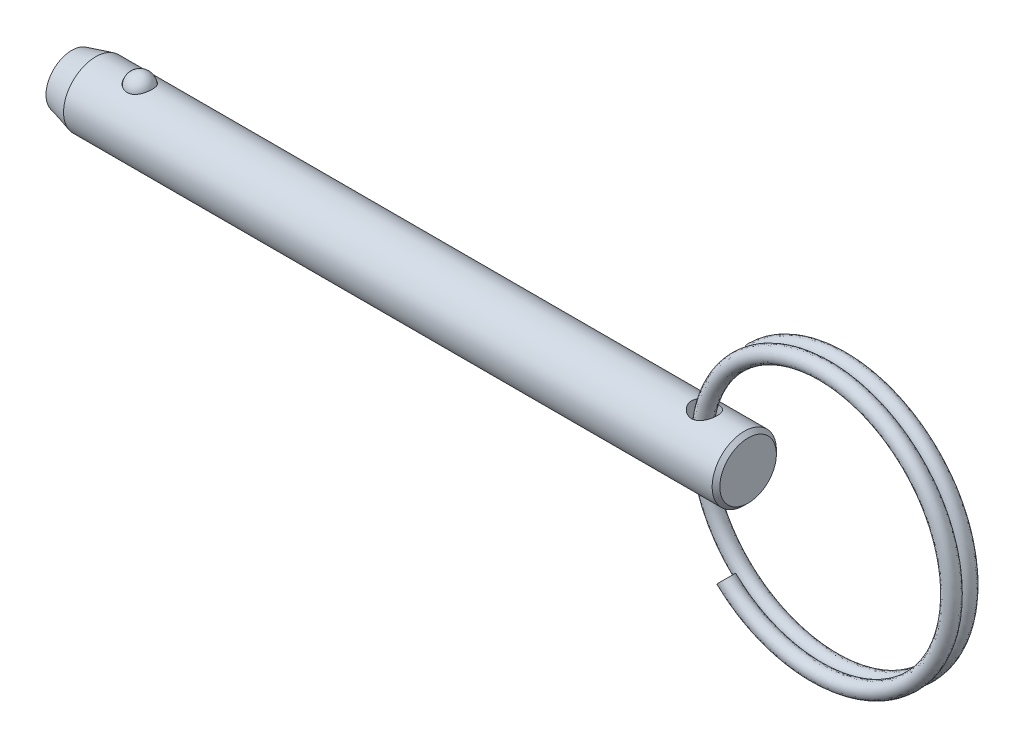
SolidWorks part; units mm, degrees
material "Plain Carbon Steel"
ref_plane "Front" through (0, 0, 0) normal (0, 0, 1) x (1, 0, 0)
ref_plane "Top" through (0, 0, 0) normal (0, 1, 0) x (1, 0, 0)
ref_plane "Right" through (0, 0, 0) normal (1, 0, 0) x (0, 0, -1)
sketch "Sketch1" plane through (0, 0, 0) normal (0, 0, 1) x (1, 0, 0)
  line L0 (33.4264, 2.794) -> (33.0454, 3.175)
  line L1 (33.0454, 3.175) -> (33.4264, 3.175) construction
  line L4 (33.4264, 2.794) -> (33.4264, 0)
  line L5 (33.4264, 3.175) -> (33.4264, 2.794) construction
  line L16 (33.0454, 3.175) -> (-31.0565, 3.175)
  line L17 (-33.4264, 3.175) -> (-33.4264, 2.54) construction
  line L19 (-31.0565, 3.175) -> (-33.4264, 3.175) construction
  line L22 (-33.4264, -3.175) -> (-31.0565, -3.175) construction
  line L23 (-26.6919, 2.8575) -> (-26.6919, -2.8575) construction
  line L24 (-33.4264, 0) -> (33.4264, 0)
  line L27 (33.4264, 0) -> (36.2204, 0) construction
  line L29 (-33.4264, 0) -> (-33.4264, -2.54) construction
  line L36 (27.8384, 0) -> (27.8384, 3.175) construction
  line L37 (-33.4264, 2.54) -> (-33.4264, 0)
  line L38 (-31.0565, -3.175) -> (33.4264, -3.175) construction
  line L39 (-33.4264, -2.54) -> (-33.4264, -3.175) construction
  line L40 (-31.0565, 3.175) -> (-33.4264, 2.54)
  line L42 (-31.0565, -3.175) -> (-33.4264, -2.54) construction
  line L43 (-31.0565, 3.175) -> (-31.0565, -3.175) construction
  circle A2 centre (-26.6919, 2.8575) radius 1.2319 construction
  point P35 (-25.5016, 3.175)
  dimension "A1" = 15
revolve "Revolve1" add sketch "Sketch1" angle 360 about L27
sketch "Sketch2" plane through (0, 0, 0) normal (0, 0, 1) x (1, 0, 0)
  line L0 (-25.4346, 2.8575) -> (-27.9492, 2.8575)
  line L1 (-26.6919, 4.0894) -> (-26.6919, 4.1148) construction
  line L2 (-25.4346, 2.8575) -> (-22.92, 2.8575) construction
  circle A0 centre (-26.6919, 2.8575) radius 1.2319 construction
  circle A1 centre (-26.6919, 2.8575) radius 1.2319 construction
  arc A2 (-27.9492, 2.8575) -> (-25.4346, 2.8575) centre (-26.6919, 2.8575) cw
  dimension "D1" = 0.0254
revolve "Cut-Revolve1" cut sketch "Sketch2" angle 360 about L2
sketch "Sketch3" plane through (0, 0, 0) normal (0, 0, 1) x (1, 0, 0)
  line L0 (-25.46, 2.8575) -> (-27.9238, 2.8575)
  line L1 (-25.46, 2.8575) -> (-22.9962, 2.8575) construction
  circle A0 centre (-26.6919, 2.8575) radius 1.2319 construction
  arc A1 (-25.46, 2.8575) -> (-27.9238, 2.8575) centre (-26.6919, 2.8575) ccw
revolve "Revolve2" add sketch "Sketch3" angle 360 about L1
sketch "Sketch4" plane through (0, 0, 0) normal (0, 0, 1) x (1, 0, 0)
  line L1 (29.1084, -3.175) -> (30.3784, -3.175)
  line L2 (29.1084, -3.175) -> (29.1084, 3.175)
  line L3 (29.1084, 3.175) -> (30.3784, 3.175)
  line L4 (30.3784, -3.175) -> (30.3784, 3.175)
  line L5 (29.1084, -3.175) -> (29.1084, -4.445) construction
  line L6 (30.3784, 3.175) -> (33.4264, 3.175) construction
  line L8 (27.8384, -3.175) -> (27.8384, 3.175) construction
  line L9 (27.8384, 0) -> (29.1084, 0) construction
  line L11 (29.1084, 0) -> (30.3784, 0) construction
  line L12 (33.0454, 3.175) -> (-31.0565, 3.175) construction
  line L14 (-31.0565, -3.175) -> (33.4264, -3.175) construction
  dimension "D1" = 2.54
revolve "Cut-Revolve2" cut sketch "Sketch4" angle 360 about L2
sketch "Sketch5" plane through (0, 0, 0) normal (0, 0, 1) x (1, 0, 0)
  line L0 (0, 0) -> (28.1314, 0) construction
  line L1 (28.1314, 0) -> (28.1314, 3.175) construction
  line L2 (33.0454, 3.175) -> (-31.0565, 3.175) construction
  line L3 (41.5934, 0) -> (55.0554, 0) construction
  line L4 (30.3784, 3.175) -> (30.0854, 3.175) construction
  line L5 (29.1084, 3.175) -> (30.3784, 3.175) construction
  line L6 (28.5112, 3.175) -> (28.5112, -3.175) construction
  line L7 (28.1314, 3.175) -> (27.8384, 3.175) construction
  line L8 (29.1084, -3.175) -> (30.3784, -3.175) construction
  line L9 (28.5112, -3.175) -> (30.3784, -3.175) construction
  line L10 (28.1314, 0) -> (41.5934, 0) construction
  line L12 (30.0854, 3.175) -> (28.5112, 3.175) construction
  line L13 (41.5934, 11.938) -> (41.5934, 13.462) construction
  circle A0 centre (41.5934, 0) radius 13.462
  circle A1 centre (41.5934, 0) radius 11.938 construction
  circle A2 centre (41.5934, 0) radius 12.7 construction
  point P26 (41.5934, 12.7)
curve "Helix/Spiral1" pitch 1.5494 height 1.3557 radius 13.462 left hand yes centre (41.5934, 0, 0) axis (0, 0, -1) start towards (1, 0, 0)
sketch "Sketch6" plane through (114.0038, 0, 0) normal (0, 1, 0) x (0, 0, -1)
  line L0 (0, 84.3484) -> (0, 85.1104) construction
  line L1 (0, 85.1104) -> (0, 85.8724) construction
  circle A0 centre (0, 85.1104) radius 0.762
  dimension "D1" = 1.524
sketch "Sketch7" plane through (0, 0, 0) normal (0, 0, 1) x (1, 0, 0)
  circle A0 centre (41.5934, 0) radius 13.462 construction
  circle A1 centre (41.5934, 0) radius 13.462
curve "Helix/Spiral2" pitch 1.5494 height 1.3557 radius 13.462 left hand yes centre (41.5934, 0, 0) axis (0, 0, 1) start towards (1, 0, 0)
sweep "Sweep1" add profiles "Sketch6" path "Helix/Spiral1"
sweep "Sweep2" add profiles "Sketch6<2>" path "Helix/Spiral2"
sketch "Sketch6<2>" plane through (114.0038, 0, 0) normal (0, 1, 0) x (0, 0, -1) same geometry as "Sketch6"
equation "\"D12@Sketch1\"=\"A@Sketch1\" * 0.80"
equation "\"D2@Sketch1\"=\"A@Sketch1\" * 0.9"
equation "\"D1@Sketch4\" = \"A@Sketch1\" / 2.5"
equation "\"Ring OD@Sketch5\" = \"R Ring Dia@Sketch5\" * 0.06"
equation "\"D4@Helix/Spiral1\"=\"Ring OD@Sketch5\" + 0.001"
equation "\"D1@Sketch6\"=\"Ring OD@Sketch5\""
equation "\"D4@Helix/Spiral2\" = \"D4@Helix/Spiral1\""
equation "\"D5@Helix/Spiral2\" = \"D5@Helix/Spiral1\""
